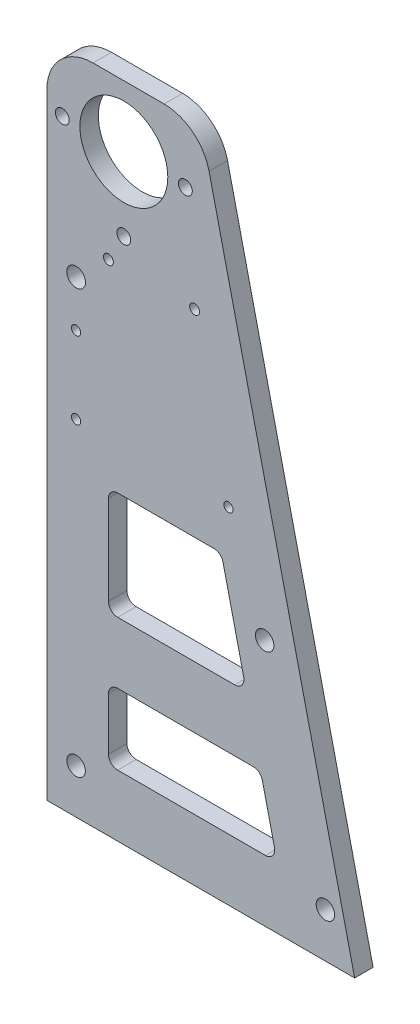
SolidWorks part; units mm, degrees
material "Policarbonato"
ref_plane "Plano frontal" through (0, 0, 0) normal (0, 0, 1) x (1, 0, 0)
ref_plane "Plano superior" through (0, 0, 0) normal (0, 1, 0) x (1, 0, 0)
ref_plane "Plano direito" through (0, 0, 0) normal (1, 0, 0) x (0, 0, -1)
sketch "Esboço1" plane through (0, 0, 0) normal (0, 0, 1) x (1, 0, 0)
  line L0 (0, 0) -> (0, 215)
  line L2 (100, 0) -> (0, 0)
  line L3 (0, 215) -> (50, 215)
  line L4 (50, 215) -> (100, 0)
  line L5 (10, 103) -> (10, 15) construction
  line L6 (25, 215) -> (25, 175) construction
  line L7 (10, 15) -> (75.7552, 15) construction
  line L8 (75.7552, 15) -> (55.2901, 103) construction
  line L9 (55.2901, 103) -> (10, 103) construction
  line L10 (20, 95) -> (20, 66)
  line L11 (23, 63) -> (61.0374, 63)
  line L12 (63.9594, 66.6795) -> (57.2152, 95.6795)
  line L13 (54.2932, 98) -> (23, 98)
  line L14 (20, 40) -> (20, 23)
  line L15 (23, 20) -> (71.0374, 20)
  line L16 (73.9594, 23.6795) -> (70.0059, 40.6795)
  line L17 (23, 43) -> (67.0839, 43)
  line L18 (0, 195) -> (50, 195) construction
  line L23 (17, 205) -> (33, 185) construction
  line L24 (17, 185) -> (33, 205) construction
  arc A8 (70.0059, 40.6795) -> (67.0839, 43) centre (67.0839, 40) ccw
  arc A9 (71.0374, 20) -> (73.9594, 23.6795) centre (71.0374, 23) ccw
  arc A10 (20, 23) -> (23, 20) centre (23, 23) ccw
  arc A11 (20, 40) -> (23, 43) centre (23, 40) cw
  arc A12 (57.2152, 95.6795) -> (54.2932, 98) centre (54.2932, 95) ccw
  arc A13 (61.0374, 63) -> (63.9594, 66.6795) centre (61.0374, 66) ccw
  arc A14 (20, 66) -> (23, 63) centre (23, 66) ccw
  arc A15 (20, 95) -> (23, 98) centre (23, 95) cw
  circle A20 centre (25, 195) radius 14.2875
  circle A21 centre (9.5, 14.5) radius 3
  point P8 (25, 195)
  point P49 (20, 63)
  dimension "D3" = 20
  dimension "D4" = 16
  dimension "D7" = 28.575
  dimension "D21" = 3
  dimension "D20" = 9.5
  dimension "D22" = 6
  dimension "D1" = 215
  dimension "D2" = 100
  dimension "D5" = 50
  dimension "D9" = 20
  dimension "D10" = 20
  dimension "D11" = 10
  dimension "D12" = 20
  dimension "D13" = 15
  dimension "D14" = 20
  dimension "D15" = 10
  dimension "D16" = 29
  dimension "D17" = 17
  dimension "D18" = 10
  dimension "D19" = 14.5
  dimension "D8" = 20
extrude "Ressalto-extrusão2" add sketch "Esboço1" along normal blind 6
fillet "Filete1" radius 15 2 edges at (0, 215, 3) (50, 215, 3)
sketch "Esboço3" plane through (0, 0, 0) normal (0, 0, -1) x (-1, 0, 0)
  line L1 (0, 0) -> (-100, 0) construction
  line L2 (0, 200) -> (0, 0) construction
  circle A0 centre (-9.5, 112) radius 1.5
  circle A1 centre (-90.5, 14.5) radius 3
  circle A2 centre (-9.5, 137) radius 1.5
  circle A3 centre (-9.5, 152) radius 3.05
  circle A4 centre (-59, 112) radius 1.5
  point P6 (-9.5, 112)
  point P9 (-9.5, 137)
  dimension "D5" = 6
  dimension "D1" = 25
  dimension "D6" = 3
  dimension "D7" = 112
  dimension "D8" = 15
  dimension "D9" = 6.1
  dimension "D10" = 49.5
  dimension "D2" = 9.5
  dimension "D3" = 14.5
  dimension "D4" = 9.5
extrude "Corte-extrusão1" cut sketch "Esboço3" against normal through all
sketch "Esboço5" plane through (0, 0, 0) normal (0, 0, -1) x (-1, 0, 0)
  line L0 (-45, 195) -> (-5, 195) construction
  circle A0 centre (-25, 171.1875) radius 2.25
  circle A1 centre (-70.7598, 80.3986) radius 3
  circle A2 centre (-25, 195) radius 14.2875 construction
  circle A3 centre (-20, 162.1875) radius 1.6
  circle A4 centre (-48, 162.1875) radius 1.6
  circle A5 centre (-45, 195) radius 2.25
  circle A6 centre (-5, 195) radius 2.25
  point P6 (-25, 195)
  point P17 (-2.75, 195)
  dimension "D1" = 23.8125
  dimension "D2" = 4.5
  dimension "D4" = 28
  dimension "D6" = 3.2
  dimension "D7" = 40
  dimension "D3" = 5
  dimension "D5" = 9
extrude "Corte-extrusão2" cut sketch "Esboço5" against normal through all
